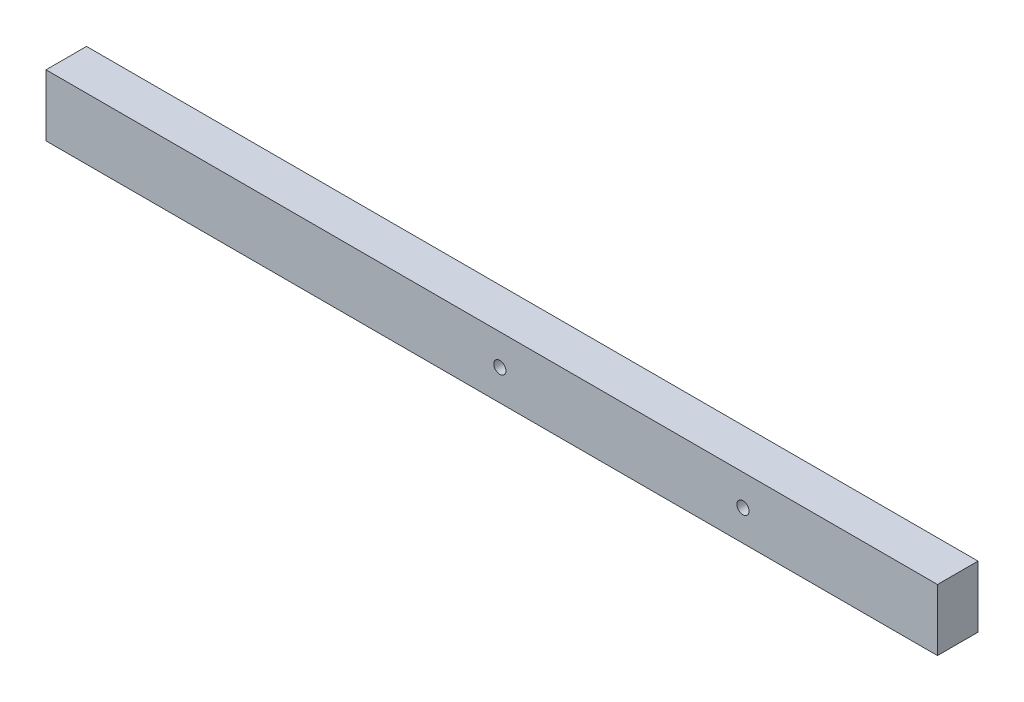
SolidWorks part; units mm, degrees
ref_plane "前视基准面" through (0, 0, 0) normal (0, 0, 1) x (1, 0, 0)
ref_plane "上视基准面" through (0, 0, 0) normal (0, 1, 0) x (1, 0, 0)
ref_plane "右视基准面" through (0, 0, 0) normal (1, 0, 0) x (0, 0, -1)
sketch "草图2" plane through (0, 0, 0) normal (0, 0, 1) x (1, 0, 0)
  line L1 (-55, 1.9) -> (0, 1.9)
  line L2 (-55, 1.9) -> (-55, -1.9)
  line L3 (-55, -1.9) -> (0, -1.9)
  line L7 (0, 1.9) -> (0, -1.9)
  circle A1 centre (-12, 0) radius 0.375
  circle A3 centre (-27, 0) radius 0.375
  dimension "D3" = 0.75
  dimension "D5" = 0.75
  dimension "D4" = 15
  dimension "D1" = 3.8
  dimension "D2" = 1.9
  dimension "D6" = 1.9
  dimension "D7" = 12
  dimension "D8" = 28
extrude "凸台-拉伸1" add sketch "草图2" along normal blind 2.5
